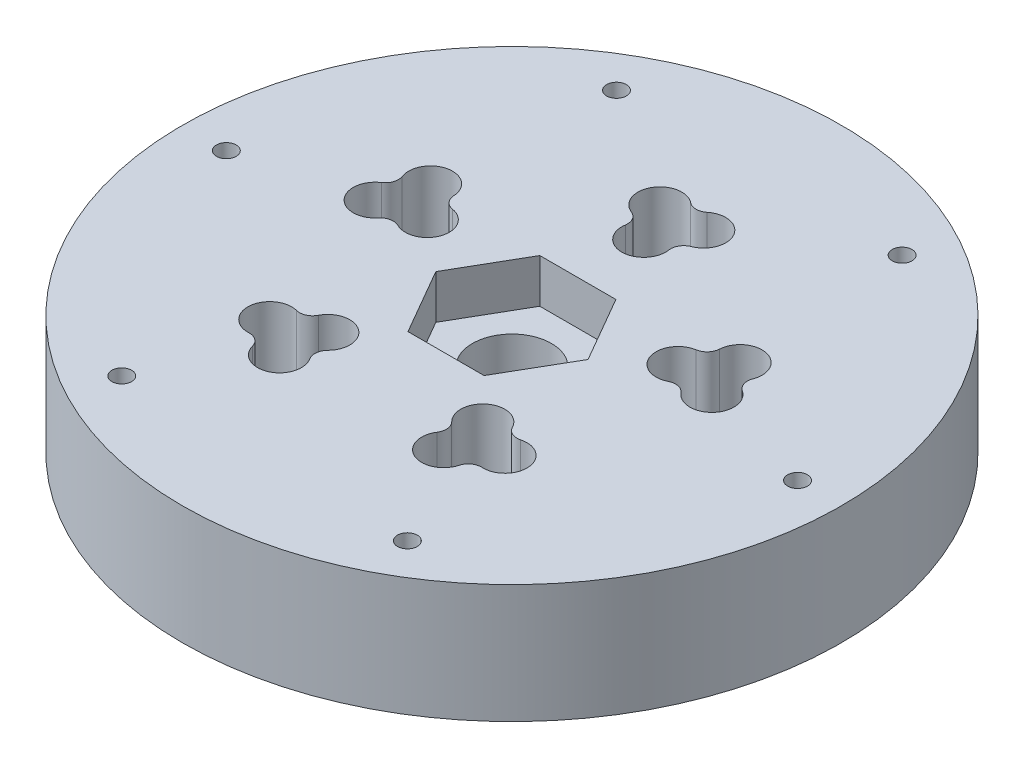
SolidWorks part; units mm, degrees
ref_plane "Front Plane" through (0, 0, 0) normal (0, 0, 1) x (1, 0, 0)
ref_plane "Top Plane" through (0, 0, 0) normal (0, 1, 0) x (1, 0, 0)
ref_plane "Right Plane" through (0, 0, 0) normal (1, 0, 0) x (0, 0, -1)
sketch "Sketch1" plane through (0, 0, 0) normal (0, 1, 0) x (1, 0, 0)
  circle A0 centre (0, 0) radius 75
  dimension "D1" = 150
extrude "Bloco" add sketch "Sketch1" against normal blind 27
sketch "Sketch2" plane through (0, 0, 0) normal (0, 1, 0) x (-1, 0, 0)
  line L0 (0, -75) -> (0, 75) construction
  line L1 (75, 0) -> (-75, 0) construction
  line L3 (-8.6603, 15) -> (-17.3205, 0)
  line L4 (-17.3205, 0) -> (-8.6603, -15)
  line L5 (-8.6603, -15) -> (8.6603, -15)
  line L6 (8.6603, -15) -> (17.3205, 0)
  line L7 (17.3205, 0) -> (8.6603, 15)
  line L8 (8.6603, 15) -> (-8.6603, 15)
  circle A0 centre (0, 0) radius 9
  circle A1 centre (0, 0) radius 75 construction
  circle A2 centre (0, 0) radius 15 construction
  point P10 (0, 15)
  dimension "D1" = 18
  dimension "D2" = 30
extrude "Furo Central - Ø18 Passante" cut sketch "Sketch2" against normal through all contours A0 region at (0, 0, 0)
extrude "Encaixe do Eixo" cut sketch "Sketch2<3>" against normal blind 10
sketch "Sketch2<3>" plane through (0, 0, 0) normal (0, 1, 0) x (-1, 0, 0) same geometry as "Sketch2"
sketch "Posição Furos de Fixação" plane through (0, -27, 0) normal (0, -1, 0) x (-1, 0, 0)
  line L0 (0, 0) -> (-65, 0) construction
  line L1 (0, 0) -> (-32.5, 56.2917) construction
  circle A0 centre (0, 0) radius 65 construction
  circle A1 centre (-32.5, 56.2917) radius 2
  circle A2 centre (32.5, 56.2917) radius 2
  circle A3 centre (65, 0) radius 2
  circle A4 centre (32.5, -56.2917) radius 2
  circle A5 centre (-32.5, -56.2917) radius 2
  circle A6 centre (-65, 0) radius 2
  point P19 (0, 0)
  dimension "D1" = 130
  dimension "D3" = 4
  dimension "D2" = 60
  dimension "D4" = 6
hole_wizard "Rebaixo - Furos de Fixação M4" positions "Sketch4" profile "Sketch5" counterbore size "M4" standard "ANSI Metric" end condition through all
sketch "Sketch4" plane through (0, -27, 0) normal (0, -1, 0) x (-1, 0, 0)
  point P0 (-32.5, 56.2917)
  point P3 (32.5, 56.2917)
  point P6 (65, 0)
  point P9 (32.5, -56.2917)
  point P12 (-32.5, -56.2917)
  point P15 (-65, 0)
sketch "Sketch5" plane through (32.5, -27, -56.2917) normal (1, 0, 0) x (0, 0, -1)
  line L0 (0, 0) -> (0, 27)
  line L1 (0, 27) -> (2.25, 27)
  line L3 (2.25, 27) -> (2.25, 4)
  line L4 (4, 4) -> (2.25, 4)
  line L5 (4, 4) -> (4, 0.025)
  line L6 (4, 0.025) -> (4.025, 0)
  line L7 (4.025, 0) -> (0, 0)
  line L8 (-4, 0.025) -> (-4.025, 0) construction
  line L11 (0, -6.35) -> (0, 107.95) construction
  dimension "Thru Hole Dia." = 4.5
  dimension "Thru Hole Depth" = 27
  dimension "C'Bore Dia." = 8
  dimension "C'Bore Depth" = 4
  dimension "Near C'Sink Dia." = 8.05
  dimension "Near C'Sink Angle" = 90
sketch "Sketch6" plane through (0, -27, 0) normal (0, -1, 0) x (-1, 0, 0)
  line L0 (0, 0) -> (0, 30) construction
  line L1 (-5, 38.6603) -> (5, 38.6603) construction
  arc A0 (-4.9427, 30.7548) -> (4.9427, 30.7548) centre (0, 30) ccw
  arc A1 (-1.875, 42.5634) -> (-6.8177, 34.0024) centre (-5, 38.6603) ccw
  arc A2 (6.8177, 34.0024) -> (1.875, 42.5634) centre (5, 38.6603) ccw
  arc A3 (-4.9427, 30.7548) -> (-6.8177, 34.0024) centre (-7.9083, 31.2076) ccw
  arc A4 (-1.875, 42.5634) -> (1.875, 42.5634) centre (0, 44.9053) ccw
  arc A5 (6.8177, 34.0024) -> (4.9427, 30.7548) centre (7.9083, 31.2076) ccw
  dimension "D2" = 10
  dimension "D4" = 6
  dimension "D1" = 30
  dimension "D3" = 10
extrude "Rasgo Dimensionado" cut sketch "Sketch6" against normal through all
pattern_circular "Rasgos" count 5 over 360 about axis through (0, -27, 0) along (0, 1, 0) of "Rasgo Dimensionado"
sketch "Sketch7" plane through (0, 0, 0) normal (1, 0, 0) x (0, 0, -1)
  line L0 (0, -27) -> (-53.5, -27)
  line L1 (-75, -27) -> (75, -27) construction
  line L2 (0, -27) -> (0, 0) construction
  circle A0 centre (-53.5, -27) radius 4
  dimension "D2" = 8
  dimension "D1" = 53.5
revolve "Canal - Raio de 4mm" cut sketch "Sketch7" angle 360 about L2 region at (0, -27, 57.3869)
